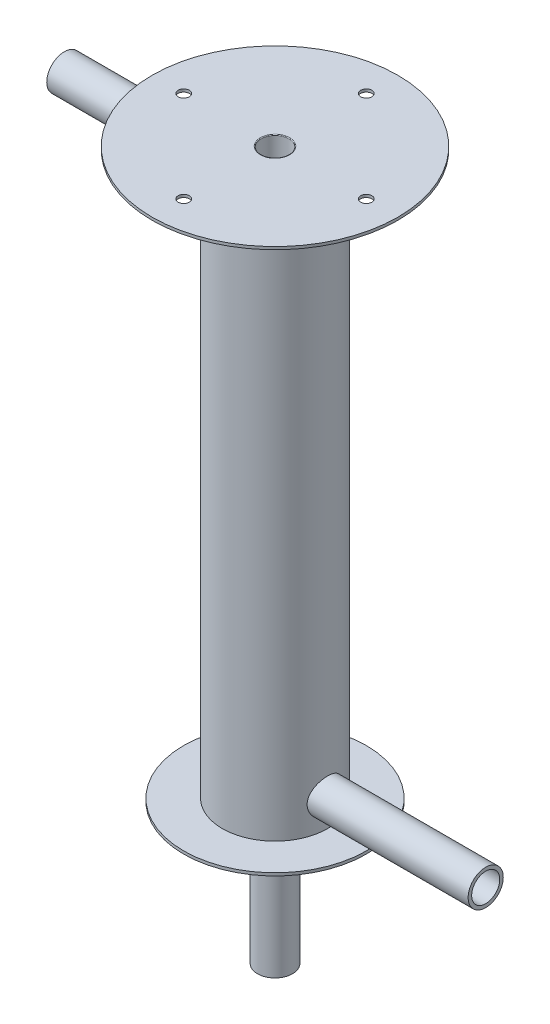
SolidWorks part; units mm, degrees
material "201 Annealed Stainless Steel (SS)"
ref_plane "Front Plane" through (0, 0, 0) normal (0, 0, 1) x (1, 0, 0)
ref_plane "Top Plane" through (0, 0, 0) normal (0, 1, 0) x (1, 0, 0)
ref_plane "Right Plane" through (0, 0, 0) normal (1, 0, 0) x (0, 0, -1)
sketch "Sketch1" plane through (0, 0, 0) normal (0, 1, 0) x (1, 0, 0)
  circle A0 centre (0, 0) radius 19.05
  dimension "D1" = 38.1
extrude "Boss-Extrude1" add sketch "Sketch1" along normal blind 203.2
sketch "Sketch2" plane through (0, 203.2, 0) normal (0, 1, 0) x (1, 0, 0)
  circle A0 centre (0, 0) radius 33.02
  dimension "D1" = 66.04
extrude "Boss-Extrude2" add sketch "Sketch2" along normal blind 1
sketch "Sketch3" plane through (0, 0, 0) normal (0, -1, 0) x (1, 0, 0)
  circle A0 centre (0, 0) radius 33.02
  dimension "D1" = 66.04
extrude "Boss-Extrude3" add sketch "Sketch3" along normal blind 1.016
shell "Shell2" thickness 1 removed face at (0, 204.2, 33.02)
ref_plane "Plane1" through (-76.2, 0, 0) normal (1, 0, 0) x (0, 0, -1)
sketch "Sketch4" plane through (-76.2, 0, 0) normal (1, 0, 0) x (0, 0, -1)
  line L0 (33.02, 204.2) -> (-33.02, 204.2) construction
  circle A0 centre (0, 189.341) radius 6.35
  dimension "D1" = 12.7
  dimension "D2" = 14.859
extrude "Boss-Extrude4" add sketch "Sketch4" along normal up to next
sketch "Sketch5" plane through (-76.2, 0, 0) normal (-1, 0, 0) x (0, 0, 1)
  circle A0 centre (0, 189.341) radius 5.08
  dimension "D1" = 10.16
extrude "Cut-Extrude1" cut sketch "Sketch5" against normal up to next
ref_plane "Plane2" through (76.2, 0, 0) normal (1, 0, 0) x (0, 0, -1)
sketch "Sketch6" plane through (76.2, 0, 0) normal (1, 0, 0) x (0, 0, -1)
  circle A0 centre (0, 10.16) radius 6.35
  dimension "D1" = 12.7
  dimension "D2" = 10.16
extrude "Boss-Extrude5" add sketch "Sketch6" against normal up to next
sketch "Sketch8" plane through (0, -1.016, 0) normal (0, -1, 0) x (1, 0, 0)
  circle A0 centre (0, 0) radius 4
  dimension "D1" = 8
extrude "Cut-Extrude3" cut sketch "Sketch8" against normal up to next
sketch "Sketch9" plane through (0, -1.016, 0) normal (0, -1, 0) x (1, 0, 0)
  circle A0 centre (0, 0) radius 6.35
  dimension "D1" = 12.7
extrude "Boss-Extrude6" add sketch "Sketch9" against normal blind 255.016 from offset 50.8
sketch "Sketch7" plane through (76.2, 0, 0) normal (1, 0, 0) x (0, 0, -1)
  circle A0 centre (0, 10.16) radius 5.08
  dimension "D1" = 10.16
extrude "Cut-Extrude2" cut sketch "Sketch7" against normal up to next
sketch "Sketch11" plane through (0, 204.2, 0) normal (0, 1, 0) x (1, 0, 0)
  circle A0 centre (0, 0) radius 44.45
  dimension "D1" = 88.9
extrude "Boss-Extrude7" add sketch "Sketch11" against normal blind 1
sketch "Sketch13" plane through (0, 204.2, 0) normal (0, 1, 0) x (1, 0, 0)
  circle A0 centre (33.02, 0) radius 2.032
  circle A1 centre (0, -33.02) radius 2.032
  circle A2 centre (-33.02, 0) radius 2.032
  circle A3 centre (0, 33.02) radius 2.032
  point P12 (0, 0)
  dimension "D1" = 4.064
  dimension "D2" = 33.02
  dimension "D3" = 4
extrude "Cut-Extrude5" cut sketch "Sketch13" against normal up to next
sketch "Sketch15" plane through (0, -51.816, 0) normal (0, -1, 0) x (1, 0, 0)
  circle A0 centre (0, 0) radius 5.08
  dimension "D1" = 10.16
extrude "Cut-Extrude6" cut sketch "Sketch15" against normal up to next
fillet "Fillet1" radius 0.254 1 edges at (0, 204.2, 5.08)
